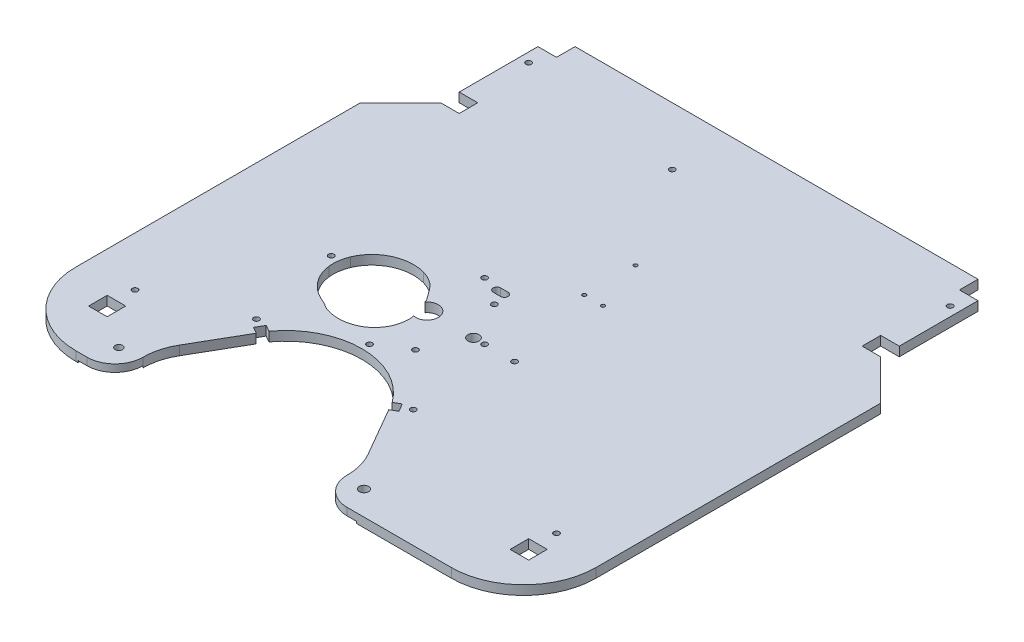
SolidWorks part; units mm, degrees
material "ABS PC"
ref_plane "Plan de face" through (0, 0, 0) normal (0, 0, 1) x (1, 0, 0)
ref_plane "Plan de dessus" through (0, 0, 0) normal (0, 1, 0) x (1, 0, 0)
ref_plane "Plan de droite" through (0, 0, 0) normal (1, 0, 0) x (0, 0, -1)
sketch "Esquisse1" plane through (0, 0, 0) normal (0, 1, 0) x (1, 0, 0)
  line L1 (-140.1, 31.2) -> (140.1, 31.2)
  line L2 (-140.1, 31.2) -> (-140.1, -245.0829)
  line L3 (-140.1, -245.0829) -> (140.1, -245.0829)
  line L4 (140.1, 31.2) -> (140.1, -245.0829)
  line L5 (45, -245.0829) -> (50, -245.0829) construction
  line L6 (-114.5, 31.2) -> (114.5, 31.2) construction
  line L7 (140.1, -4) -> (140.1, 4) construction
  line L8 (-140.1, 4) -> (-140.1, -4) construction
extrude "Boss.-Extru.1" add sketch "Esquisse1" along normal blind 5
sketch "Esquisse2" plane through (0, 0, 0) normal (0, 1, 0) x (1, 0, 0)
  line L3 (-58.1815, -184) -> (-61.6457, -182)
  line L4 (-61.6457, -182) -> (-64.1457, -186.3301)
  line L5 (-64.1457, -186.3301) -> (-60.6815, -188.3301)
  line L7 (-25, -132) -> (-25, -245.0829) construction
  line L8 (-58.1815, -184) -> (-60.6815, -188.3301) construction
  line L9 (-62.6323, -132) -> (62.6323, -132) construction
  line L10 (-25, -62.6323) -> (-25, 62.6323) construction
  line L11 (-60.6815, -188.3301) -> (-75.8539, -214.6094)
  line L13 (-58.1815, -184) -> (-54.7174, -186) construction
  line L14 (-25, -168.5125) -> (-25, -231.5125) construction
  line L16 (140.1, -245.0829) -> (-140.1, -245.0829) construction
  line L17 (-140.1, -245.0829) -> (140.1, -245.0829) construction
  line L18 (8.1815, -184) -> (4.7174, -186) construction
  line L20 (8.1815, -184) -> (10.6815, -188.3301) construction
  line L21 (10.6815, -188.3301) -> (25.8539, -214.6094)
  line L22 (14.1457, -186.3301) -> (10.6815, -188.3301)
  line L23 (11.6457, -182) -> (14.1457, -186.3301)
  line L24 (8.1815, -184) -> (11.6457, -182)
  line L25 (-62.8957, -184.1651) -> (-67.2258, -181.6651) construction
  line L26 (-95, -245.0829) -> (45, -245.0829)
  arc A0 (-95, -245.0829) -> (-86.2863, -217.8734) centre (-95, -230.0829) ccw construction
  arc A1 (8.1815, -184) -> (-58.1815, -184) centre (-25, -208.0829) ccw
  arc A2 (-95, -245.0829) -> (-80, -230.0829) centre (-95, -230.0829) ccw
  arc A4 (-80, -230.0829) -> (-75.8539, -214.6094) centre (-49.0531, -230.0829) cw
  arc A5 (30, -230.0829) -> (25.8539, -214.6094) centre (-0.9469, -230.0829) ccw
  arc A6 (45, -245.0829) -> (30, -230.0829) centre (45, -230.0829) cw
  circle A8 centre (-67.2258, -181.6651) radius 1.5
  circle A10 centre (17.2258, -181.6651) radius 1.5
  dimension "D4" = 41
  dimension "D8" = 5
  dimension "D9" = 3
  dimension "D1" = 4
  dimension "D2" = 52
  dimension "D3" = 37
  dimension "D5" = 90
  dimension "D6" = 5
  dimension "D7" = 30
extrude "Enlèv. mat.-Extru.2" cut sketch "Esquisse2" along normal through all
sketch "Esquisse3" plane through (0, 5, 0) normal (0, 1, 0) x (1, 0, 0)
  line L0 (-30.2198, -127.0596) -> (-26.1089, -139.1328)
  spline S0 degree 3 poles (-37.7914, -122.1402) (-38.0734, -121.8243) (-38.3657, -121.5165) (-38.9965, -120.9381) (-39.3221, -120.6716) (-39.9982, -120.1678) (-40.3476, -119.9323) (-41.0674, -119.4915) (-41.4393, -119.2855) (-41.8168, -119.0963) knots 0 0 0 0 0.25 0.25 0.5 0.5 0.75 0.75 1 1 1 1 construction
  spline S1 degree 3 poles (-32.1541, -129.7487) (-32.3725, -129.4202) (-32.6019, -129.0988) (-33.0628, -128.4574) (-33.2929, -128.1364) (-33.9829, -127.1734) (-34.442, -126.5306) (-35.3645, -125.2486) (-35.8282, -124.6096) (-36.7788, -123.3501) (-37.2654, -122.7294) (-37.7914, -122.1402) knots 0 0 0 0 0.125 0.125 0.25 0.25 0.5 0.5 0.75 0.75 1 1 1 1 construction
  spline S2 degree 3 poles (-35.6619, -154.1946) (-35.0242, -153.7971) (-34.4156, -153.3543) (-33.5487, -152.619) (-33.2665, -152.3609) (-32.7231, -151.8244) (-32.4631, -151.5476) (-31.717, -150.6924) (-31.2669, -150.0877) (-30.6603, -149.1305) (-30.4697, -148.8029) (-30.1129, -148.13) (-29.9465, -147.7839) (-29.4899, -146.7378) (-29.243, -146.0234) (-28.8562, -144.563) (-28.7157, -143.8147) (-28.4532, -141.5381) (-28.491, -140.0256) (-28.7111, -138.5175) knots 0 0 0 0 0.125 0.125 0.1875 0.1875 0.25 0.25 0.375 0.375 0.4375 0.4375 0.5 0.5 0.625 0.625 0.75 0.75 1 1 1 1 construction
  spline S3 degree 3 poles (-35.6619, -154.1946) (-36.3253, -154.608) (-37.0218, -154.968) (-38.4509, -155.5833) (-39.1871, -155.8402) (-40.6929, -156.2533) (-41.4552, -156.4075) (-42.998, -156.615) (-43.7804, -156.6676) (-46.0993, -156.6733) (-47.6259, -156.4799) (-49.5088, -155.9804) (-49.8836, -155.8673) (-50.622, -155.6166) (-50.9867, -155.4786) (-51.7066, -155.1765) (-52.0616, -155.0123) (-52.5826, -154.748) (-52.7564, -154.66) (-53.0886, -154.4564) (-53.2465, -154.3401) (-53.4028, -154.2206) knots 0 0 0 0 0.125 0.125 0.25 0.25 0.375 0.375 0.5 0.5 0.75 0.75 0.8125 0.8125 0.875 0.875 0.9375 0.9375 0.96875 0.96875 1 1 1 1 construction
  spline S4 degree 3 poles (-41.8168, -119.0963) (-42.9717, -118.5173) (-44.1778, -118.0898) (-46.0518, -117.6406) (-46.691, -117.5235) (-47.9689, -117.3572) (-48.6085, -117.3074) (-49.8889, -117.2725) (-50.5296, -117.2869) (-51.8124, -117.3808) (-52.4575, -117.4608) (-54.3583, -117.7944) (-55.5875, -118.1406) (-57.3737, -118.8468) (-57.9613, -119.1147) (-59.1074, -119.714) (-59.6598, -120.0407) (-61.253, -121.1053) (-62.2339, -121.9217) (-63.3433, -123.0959) (-63.5595, -123.3389) (-63.9727, -123.8343) (-64.1705, -124.0875) (-64.7392, -124.8624) (-65.0859, -125.3992) (-65.725, -126.5066) (-66.0166, -127.0778) (-66.4118, -127.9607) (-66.5364, -128.2602) (-66.7677, -128.8619) (-66.8752, -129.1647) (-67.3727, -130.6881) (-67.6417, -131.9376) (-67.7975, -133.5423) (-67.8198, -133.8663) (-67.8456, -134.511) (-67.8492, -134.8322) (-67.832, -135.7928) (-67.7828, -136.429) (-67.6138, -137.6932) (-67.494, -138.3213) (-67.1803, -139.5691) (-66.9857, -140.1898) (-66.3106, -141.9951) (-65.7352, -143.1386) (-64.7029, -144.7728) (-64.3296, -145.3033) (-63.5406, -146.3156) (-63.1238, -146.8009) (-62.2475, -147.7313) (-61.7884, -148.177) (-60.8134, -149.015) (-60.2997, -149.4102) (-59.6532, -149.8941) (-59.524, -149.9912) (-59.2621, -150.18) (-59.1281, -150.2696) (-58.7233, -150.5349) (-58.4482, -150.704) (-57.6091, -151.1904) (-57.0301, -151.4842) (-56.1848, -151.9623) (-55.907, -152.1283) (-55.4954, -152.386) (-55.361, -152.4765) (-55.1045, -152.6783) (-54.9822, -152.7884) (-54.7446, -153.015) (-54.6281, -153.1308) (-54.3929, -153.36) (-54.2744, -153.4736) (-53.9142, -153.8089) (-53.6638, -154.0209) (-53.4028, -154.2206) knots 0 0 0 0 0.0625 0.0625 0.09375 0.09375 0.125 0.125 0.15625 0.15625 0.1875 0.1875 0.25 0.25 0.28125 0.28125 0.3125 0.3125 0.375 0.375 0.390625 0.390625 0.40625 0.40625 0.4375 0.4375 0.46875 0.46875 0.484375 0.484375 0.5 0.5 0.5625 0.5625 0.578125 0.578125 0.59375 0.59375 0.625 0.625 0.65625 0.65625 0.6875 0.6875 0.75 0.75 0.78125 0.78125 0.8125 0.8125 0.84375 0.84375 0.875 0.875 0.882812 0.882812 0.890625 0.890625 0.90625 0.90625 0.9375 0.9375 0.953125 0.953125 0.960937 0.960937 0.96875 0.96875 0.976562 0.976562 0.984375 0.984375 1 1 1 1 construction
  spline S30 degree 3 poles (-26.1089, -139.1328) (-25.957, -141.5638) (-26.2233, -144.068) (-26.9566, -146.3908) knots 0 0 0 0 1 1 1 1
  spline S31 degree 3 poles (-26.9566, -146.3908) (-27.2228, -147.2342) (-27.8831, -148.8893) (-29.2029, -151.171) (-30.8763, -153.2749) (-32.1537, -154.4712) (-32.834, -155.0244) knots 0 0 0 0 0.25 0.5 0.75 1 1 1 1
  spline S32 degree 3 poles (-32.834, -155.0244) (-34.0816, -156.0391) (-36.8741, -157.7375) (-39.9456, -158.6891) (-41.5144, -158.9883) knots 0 0 0 0 0.5 1 1 1 1
  spline S33 degree 3 poles (-41.5144, -158.9883) (-44.1178, -159.4848) (-46.8613, -159.4832) (-49.4654, -158.9908) knots 0 0 0 0 1 1 1 1
  spline S34 degree 3 poles (-49.4654, -158.9908) (-49.952, -158.8988) (-50.9201, -158.6805) (-51.9843, -158.3611) (-52.6895, -158.1153) (-53.0279, -157.9903) (-53.4112, -157.8436) (-53.8185, -157.6386) (-54.1411, -157.4539) (-54.4726, -157.2537) (-54.8017, -157.0368) (-54.9983, -156.9002) (-55.0989, -156.8301) knots 0 0 0 0 0.25 0.5 0.5625 0.625 0.6875 0.75 0.8125 0.875 0.9375 1 1 1 1
  spline S35 degree 3 poles (-55.0989, -156.8301) (-55.3218, -156.6748) (-55.8004, -156.3308) (-56.3372, -156.039) (-57.1153, -155.7047) (-58.1073, -155.2831) (-59.4212, -154.7248) (-60.6952, -154.0815) (-61.7162, -153.4751) (-62.6513, -152.8651) (-64.3061, -151.7169) (-66.4424, -149.811) (-68.6708, -147.1371) (-71.0288, -143.199) (-72.0496, -139.8117) (-72.3207, -137.531) knots 0 0 0 0 0.03125 0.0625 0.09375 0.125 0.1875 0.25 0.28125 0.3125 0.375 0.5 0.625 0.75 1 1 1 1
  spline S36 degree 3 poles (-72.3207, -137.531) (-72.524, -135.8208) (-72.4832, -132.3293) (-71.5647, -128.9796) (-70.9127, -127.3896) knots 0 0 0 0 0.5 1 1 1 1
  spline S37 degree 3 poles (-70.9127, -127.3896) (-70.401, -126.1419) (-69.1411, -123.7476) (-66.5657, -120.5334) (-63.4815, -117.9312) (-59.9208, -115.9009) (-56.1194, -114.5638) (-52.0895, -113.8994) (-48.0382, -113.9466) (-45.3685, -114.4522) (-44.0724, -114.8246) knots 0 0 0 0 0.125 0.25 0.375 0.5 0.625 0.75 0.875 1 1 1 1
  spline S38 degree 3 poles (-44.0724, -114.8246) (-43.1335, -115.0943) (-41.3015, -115.7539) (-39.094, -116.9388) (-37.4723, -118.0859) (-36.3006, -119.1013) (-35.2972, -120.193) (-34.6853, -120.94) (-34.3845, -121.3211) knots 0 0 0 0 0.25 0.5 0.625 0.75 0.875 1 1 1 1
  spline S39 degree 3 poles (-34.3845, -121.3211) (-33.6538, -122.2469) (-32.5988, -123.6857) (-31.2416, -125.568) (-30.5443, -126.5566) (-30.2198, -127.0596) knots 0 0 0 0 0.5 0.75 1 1 1 1
  spline S40 degree 3 poles (-544.0684, -2053.4709) (-13.3203, -329.9447) (2.5957, -129.3013) (-46.0518, -117.6406) (-46.691, -117.5235) (-47.9689, -117.3572) (-48.6085, -117.3074) (-49.8889, -117.2725) (-50.5296, -117.2869) (-51.8124, -117.3808) (-52.4575, -117.4608) (-54.3583, -117.7944) (-55.5875, -118.1406) (-57.3737, -118.8468) (-57.9613, -119.1147) (-59.1074, -119.714) (-59.6598, -120.0407) (-61.253, -121.1053) (-62.2339, -121.9217) (-63.3433, -123.0959) (-63.5595, -123.3389) (-63.9727, -123.8343) (-64.1705, -124.0875) (-64.7392, -124.8624) (-65.0859, -125.3992) (-65.725, -126.5066) (-66.0166, -127.0778) (-66.4118, -127.9607) (-66.5364, -128.2602) (-66.7677, -128.8619) (-66.8752, -129.1647) (-67.3727, -130.6881) (-67.6417, -131.9376) (-67.7975, -133.5423) (-67.8198, -133.8663) (-67.8456, -134.511) (-67.8492, -134.8322) (-67.832, -135.7928) (-67.7828, -136.429) (-67.6138, -137.6932) (-67.494, -138.3213) (-67.1803, -139.5691) (-66.9857, -140.1898) (-66.3106, -141.9951) (-65.7352, -143.1386) (-64.7029, -144.7728) (-64.3296, -145.3033) (-63.5406, -146.3156) (-63.1238, -146.8009) (-62.2475, -147.7313) (-61.7884, -148.177) (-60.8134, -149.015) (-60.2997, -149.4102) (-59.6532, -149.8941) (-59.524, -149.9912) (-59.2621, -150.18) (-59.1281, -150.2696) (-58.7233, -150.5349) (-58.4482, -150.704) (-57.6091, -151.1904) (-57.0301, -151.4842) (-56.1848, -151.9623) (-55.907, -152.1283) (-55.4954, -152.386) (-55.361, -152.4765) (-55.1045, -152.6783) (-54.9822, -152.7884) (-54.7446, -153.015) (-54.6281, -153.1308) (-54.3929, -153.36) (-54.2744, -153.4736) (-26.8241, -179.0197) (131.7308, -54.8381) (1346.14, 1273.1767) knots -2.339844 -2.339844 -2.339844 -2.339844 0.0625 0.0625 0.09375 0.09375 0.125 0.125 0.15625 0.15625 0.1875 0.1875 0.25 0.25 0.28125 0.28125 0.3125 0.3125 0.375 0.375 0.390625 0.390625 0.40625 0.40625 0.4375 0.4375 0.46875 0.46875 0.484375 0.484375 0.5 0.5 0.5625 0.5625 0.578125 0.578125 0.59375 0.59375 0.625 0.625 0.65625 0.65625 0.6875 0.6875 0.75 0.75 0.78125 0.78125 0.8125 0.8125 0.84375 0.84375 0.875 0.875 0.882812 0.882812 0.890625 0.890625 0.90625 0.90625 0.9375 0.9375 0.953125 0.953125 0.960937 0.960937 0.96875 0.96875 0.976562 0.976562 0.984375 0.984375 2.762304 2.762304 2.762304 2.762304 only from (-41.8168, -119.0963) to (-53.4028, -154.2206)
  spline S41 degree 3 poles (-1939.2427, 445.2377) (-11.3915, 5.3531) (-2.0926, -139.9279) (-38.4509, -155.5833) (-39.1871, -155.8402) (-40.6929, -156.2533) (-41.4552, -156.4075) (-42.998, -156.615) (-43.7804, -156.6676) (-46.0993, -156.6733) (-47.6259, -156.4799) (-49.5088, -155.9804) (-49.8836, -155.8673) (-50.622, -155.6166) (-50.9867, -155.4786) (-51.7066, -155.1765) (-52.0616, -155.0123) (-52.5826, -154.748) (-52.7564, -154.66) (-62.008, -148.9921) (-46.7728, -99.7044) (-1052.7685, -1886.2862) knots -6.110057 -6.110057 -6.110057 -6.110057 0.125 0.125 0.25 0.25 0.375 0.375 0.5 0.5 0.75 0.75 0.8125 0.8125 0.875 0.875 0.9375 0.9375 0.96875 0.96875 2.678123 2.678123 2.678123 2.678123 only from (-35.6619, -154.1946) to (-53.4028, -154.2206)
  spline S42 degree 3 poles (805.3246, -1958.3687) (-625.9447, 427.7737) (-104.0787, -212.4384) (-33.5487, -152.619) (-33.2665, -152.3609) (-32.7231, -151.8244) (-32.4631, -151.5476) (-31.717, -150.6924) (-31.2669, -150.0877) (-30.6603, -149.1305) (-30.4697, -148.8029) (-30.1129, -148.13) (-29.9465, -147.7839) (-29.4899, -146.7378) (-29.243, -146.0234) (-28.8562, -144.563) (-28.7157, -143.8147) (-20.1781, -69.7717) (-507.9815, -8.4894) (1948.7508, 124.0064) knots -15.067184 -15.067184 -15.067184 -15.067184 0.125 0.125 0.1875 0.1875 0.25 0.25 0.375 0.375 0.4375 0.4375 0.5 0.5 0.625 0.625 0.75 0.75 12.82174 12.82174 12.82174 12.82174 only from (-35.6619, -154.1946) to (-28.7111, -138.5175)
  spline S43 degree 3 poles (-1678.0425, -1265.3241) (-10.5484, -165.9011) (-20.1896, -146.3733) (-33.0628, -128.4574) (-33.2929, -128.1364) (-33.9829, -127.1734) (-34.442, -126.5306) (-35.3645, -125.2486) (-35.8282, -124.6096) (-54.2717, -100.1715) (-88.436, -89.3419) (-1650.9877, -1303.2795) knots -6.732601 -6.732601 -6.732601 -6.732601 0.125 0.125 0.25 0.25 0.5 0.5 0.75 0.75 10.201277 10.201277 10.201277 10.201277 only from (-32.1541, -129.7487) to (-37.7914, -122.1402)
  spline S44 degree 3 poles (1561.6634, 1077.8271) (-67.121, -199.6011) (-22.5068, -136.058) (-38.9965, -120.9381) (-39.3221, -120.6716) (-39.9982, -120.1678) (-40.3476, -119.9323) (-65.1031, -104.7717) (-144.7605, -156.1255) (1752.928, -999.5442) knots -12.570471 -12.570471 -12.570471 -12.570471 0.25 0.25 0.5 0.5 0.75 0.75 17.69557 17.69557 17.69557 17.69557 only from (-37.7914, -122.1402) to (-41.8168, -119.0963)
extrude "Enlèv. mat.-Extru.3" cut sketch "Esquisse3" against normal through all
sketch "Esquisse4" plane through (0, 5, 0) normal (0, 1, 0) x (1, 0, 0)
  circle A0 centre (19.9, -82.15) radius 1
  circle A1 centre (9.8, -82.15) radius 1
  circle A2 centre (9.8, -54.55) radius 1
  dimension "D1" = 2
extrude "Enlèv. mat.-Extru.4" cut sketch "Esquisse4" against normal through all
sketch "Esquisse5" plane through (0, 5, 0) normal (0, 1, 0) x (1, 0, 0)
  circle A0 centre (22.1224, -132) radius 1.5
  circle A1 centre (-10.0508, -153.25) radius 1.5
  circle A2 centre (-25, -163) radius 1.5
  circle A3 centre (-10.0508, -110.75) radius 1.5
  circle A4 centre (-25, -101) radius 1.5
  circle A5 centre (-76.6, -132) radius 1.5
  circle A6 centre (6, -132) radius 1.5 construction
  circle A7 centre (6, -132) radius 1.5
  circle A8 centre (0, -132) radius 3
  arc A9 (1.5616, -134.5616) -> (1.5616, -129.4384) centre (0, -132) ccw construction
  circle A10 centre (-10.0508, -110.75) radius 1.5 construction
  dimension "D1" = 3
extrude "Enlèv. mat.-Extru.5" cut sketch "Esquisse5" against normal through all
sketch "Esquisse6" plane through (0, 5, 0) normal (0, 1, 0) x (1, 0, 0)
  circle A0 centre (-25, -132) radius 6
  circle A1 centre (-25, -132) radius 5.4 construction
  dimension "D1" = 12
extrude "Enlèv. mat.-Extru.6" cut sketch "Esquisse6" against normal through all
sketch "Esquisse7" plane through (0, 5, 0) normal (0, 1, 0) x (1, 0, 0)
  line L1 (-16, -103.4) -> (-12, -103.4) construction
  line L2 (-16, -101.4) -> (-12, -101.4)
  line L3 (-16, -105.4) -> (-12, -105.4)
  arc A0 (-16, -101.4) -> (-16, -105.4) centre (-16, -103.4) ccw
  arc A6 (-12, -105.4) -> (-12, -101.4) centre (-12, -103.4) ccw
  arc A7 (-11.4091, -103.2958) -> (-12.5909, -103.2958) centre (-12, -103.4) ccw construction
  arc A9 (-15.4091, -103.2958) -> (-16.5909, -103.2958) centre (-16, -103.4) ccw construction
  point P2 (-14, -103.4)
  dimension "D1" = 4
extrude "Enlèv. mat.-Extru.7" cut sketch "Esquisse7" against normal through all
sketch "Esquisse8" plane through (0, 5, 0) normal (0, 1, 0) x (1, 0, 0)
  line L0 (140.1, -245.0829) -> (140.1, 31.2) construction
  line L1 (101.1, -245.0829) -> (140.1, -245.0829)
  line L2 (140.1, -245.0829) -> (140.1, -206.0829)
  line L3 (-140.1, -245.0829) -> (-140.1, -206.0829)
  line L4 (-140.1, 31.2) -> (-140.1, -245.0829) construction
  line L5 (-140.1, -245.0829) -> (-95, -245.0829) construction
  line L6 (-101.1, -245.0829) -> (-140.1, -245.0829)
  arc A0 (140.1, -206.0829) -> (101.1, -245.0829) centre (101.1, -206.0829) cw
  arc A1 (-140.1, -206.0829) -> (-101.1, -245.0829) centre (-101.1, -206.0829) ccw
extrude "Enlèv. mat.-Extru.8" cut sketch "Esquisse8" against normal through all
sketch "Esquisse9" plane through (0, 5, 0) normal (0, 1, 0) x (1, 0, 0)
  line L0 (-108.5, 21.2) -> (-118.5, 21.2) construction
  line L1 (-108.5, 21.2) -> (-108.5, 31.2) construction
  line L2 (-108.5, -31.2) -> (-108.5, -21.2) construction
  line L3 (-108.5, -21.2) -> (-118.5, -21.2) construction
  line L4 (-108.5, -31.2) -> (-118.5, -31.2) construction
  line L5 (-108.5, 21.2) -> (-118.5, 21.2)
  line L6 (-108.5, 21.2) -> (-108.5, 31.2)
  line L7 (-108.5, -31.2) -> (-108.5, -21.2)
  line L8 (-108.5, -21.2) -> (-118.5, -21.2)
  line L9 (-108.5, -31.2) -> (-118.5, -31.2)
  line L10 (-118.5, -21.2) -> (-118.5, 21.2)
  line L11 (-118.5, -31.2) -> (-140.1, -52.8)
  line L12 (-140.1, 31.2) -> (-140.1, -206.0829) construction
  line L13 (-140.1, -52.8) -> (-140.1, 31.2)
  line L14 (-140.1, 31.2) -> (-108.5, 31.2)
  line L15 (0, 0) -> (0, 79.4635) construction
  line L16 (140.1, 31.2) -> (108.5, 31.2)
  line L17 (140.1, -52.8) -> (140.1, 31.2)
  line L18 (118.5, -31.2) -> (140.1, -52.8)
  line L19 (118.5, -21.2) -> (118.5, 21.2)
  line L20 (108.5, -31.2) -> (118.5, -31.2)
  line L21 (108.5, -21.2) -> (118.5, -21.2)
  line L22 (108.5, -31.2) -> (108.5, -21.2)
  line L23 (108.5, 21.2) -> (108.5, 31.2)
  line L24 (108.5, 21.2) -> (118.5, 21.2)
  dimension "D1" = 45
extrude "Enlèv. mat.-Extru.9" cut sketch "Esquisse9" against normal through all
sketch "Esquisse10" plane through (0, 0, 0) normal (0, -1, 0) x (1, 0, 0)
  line L1 (-100, 245.0829) -> (-100, 242.0829) construction
  line L2 (-95, 242.0829) -> (-100, 242.0829) construction
  line L4 (45, 242.0829) -> (50, 242.0829) construction
  line L5 (50, 242.0829) -> (50, 245.0829)
  line L6 (50, 245.0829) -> (45, 245.0829)
  line L7 (45, 242.0829) -> (50, 242.0829)
  line L8 (50, 245.0829) -> (50, 242.0829) construction
  line L9 (-101.1, 245.0829) -> (-95, 245.0829) construction
  line L11 (45, 245.0829) -> (50, 245.0829) construction
  line L20 (-95, 245.0829) -> (-100, 245.0829)
  line L21 (-100, 245.0829) -> (-100, 242.0829)
  line L22 (-100, 242.0829) -> (-95, 242.0829)
  arc A0 (-88.029, 220.3153) -> (-25, 23.5) centre (-25, 132) ccw construction
  arc A1 (-86.2863, 217.8734) -> (-25, 26.5) centre (-25, 132) ccw construction
  arc A2 (-25, 26.5) -> (50, 206.1974) centre (-25, 132) ccw construction
  arc A3 (-25, 23.5) -> (50, 210.4044) centre (-25, 132) ccw construction
  arc A4 (-88.029, 220.3153) -> (-25, 23.5) centre (-25, 132) ccw
  arc A5 (-86.2863, 217.8734) -> (-25, 26.5) centre (-25, 132) ccw
  arc A6 (-25, 26.5) -> (36.2863, 217.8734) centre (-25, 132) ccw
  arc A7 (-25, 23.5) -> (38.029, 220.3153) centre (-25, 132) ccw
  arc A8 (45, 245.0829) -> (36.2863, 217.8734) centre (45, 230.0829) ccw construction
  arc A10 (45, 245.0829) -> (36.2863, 217.8734) centre (45, 230.0829) ccw
  arc A11 (45, 242.0829) -> (38.029, 220.3153) centre (45, 230.0829) ccw
  arc A12 (45, 242.0829) -> (38.029, 220.3153) centre (45, 230.0829) ccw construction
  arc A14 (-88.029, 220.3153) -> (-95, 242.0829) centre (-95, 230.0829) ccw construction
  arc A15 (-80, 230.0829) -> (-95, 245.0829) centre (-95, 230.0829) ccw construction
  arc A16 (-86.2863, 217.8734) -> (-95, 245.0829) centre (-95, 230.0829) ccw
  arc A17 (-88.029, 220.3153) -> (-95, 242.0829) centre (-95, 230.0829) ccw
extrude "Enlèv. mat.-Extru.10" cut sketch "Esquisse10" against normal blind 1
sketch "Esquisse11" plane through (0, 5, 0) normal (0, 1, 0) x (1, 0, 0)
  line L4 (-118.5, -210.8) -> (-118.5, -220.8)
  line L5 (-108.5, -210.8) -> (-118.5, -210.8)
  line L6 (-108.5, -220.8) -> (-108.5, -210.8)
  line L7 (-118.5, -220.8) -> (-108.5, -220.8)
  line L8 (-118.5, -210.8) -> (-118.5, -220.8)
  line L9 (-108.5, -210.8) -> (-118.5, -210.8)
  line L10 (-108.5, -220.8) -> (-108.5, -210.8)
  line L11 (-118.5, -220.8) -> (-108.5, -220.8)
  line L12 (108.5, -210.8) -> (108.5, -220.8)
  line L13 (118.5, -210.8) -> (108.5, -210.8)
  line L14 (118.5, -220.8) -> (118.5, -210.8)
  line L15 (108.5, -220.8) -> (118.5, -220.8)
  line L16 (108.5, -210.8) -> (108.5, -220.8)
  line L17 (118.5, -210.8) -> (108.5, -210.8)
  line L18 (118.5, -220.8) -> (118.5, -210.8)
  line L19 (108.5, -220.8) -> (118.5, -220.8)
  dimension "D1" = 0
  dimension "D2" = 0
extrude "Enlèv. mat.-Extru.11" cut sketch "Esquisse11" against normal through all
sketch "Esquisse12" plane through (0, 5, 0) normal (0, 1, 0) x (1, 0, 0)
  circle A0 centre (41, -232) radius 2.5 construction
  circle A1 centre (41, -232) radius 2.5
  circle A2 centre (-91, -232) radius 2 construction
  circle A3 centre (-91, -232) radius 2
extrude "Enlèv. mat.-Extru.12" cut sketch "Esquisse12" against normal through all
sketch "Esquisse13" plane through (0, 5, 0) normal (0, 1, 0) x (1, 0, 0)
  circle A0 centre (-113.5, -200.8) radius 1.5
  circle A1 centre (-113.5, 11.2) radius 1.5
  circle A2 centre (-113.5, 11.2) radius 1.525 construction
  circle A3 centre (-113.5, -200.8) radius 1.525 construction
  circle A4 centre (113.5, 11.2) radius 1.5
  circle A5 centre (113.5, -200.8) radius 1.5
  circle A6 centre (113.5, -200.8) radius 1.25 construction
  circle A7 centre (-25, 0) radius 1.5
  circle A9 centre (-25, 0) radius 1.5 construction
  dimension "D1" = 3
extrude "Enlèv. mat.-Extru.15" cut sketch "Esquisse13" against normal through all
